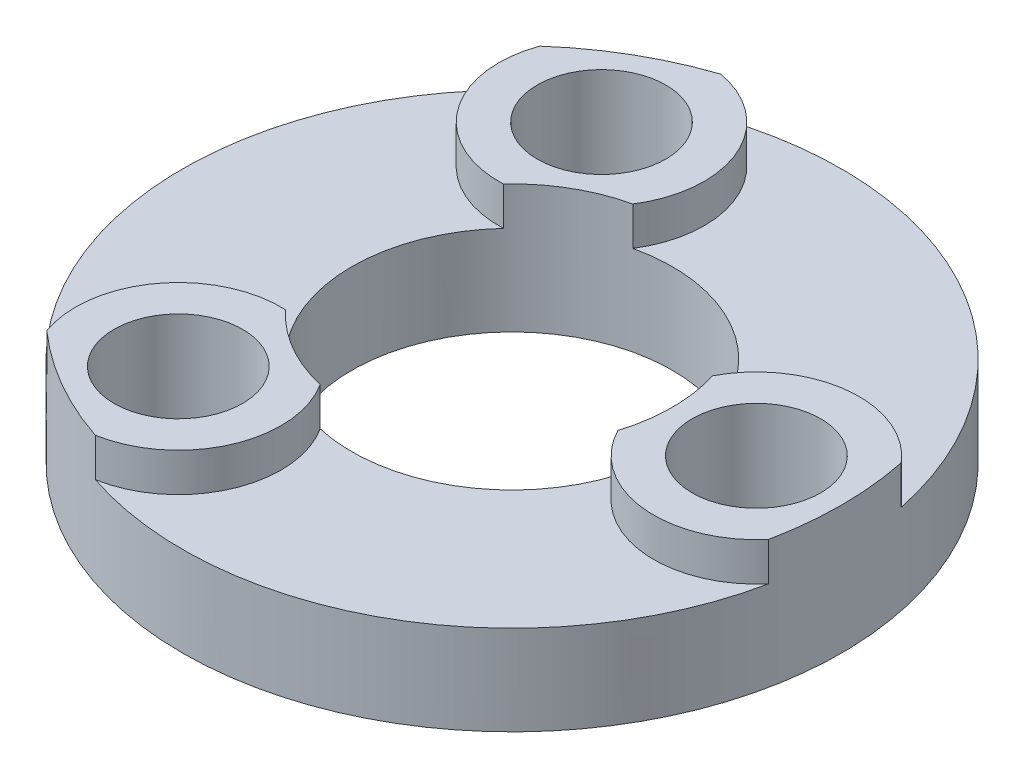
SolidWorks part; units mm, degrees
material "ABS"
ref_plane "Front Plane" through (0, 0, 0) normal (0, 0, 1) x (1, 0, 0)
ref_plane "Top Plane" through (0, 0, 0) normal (0, 1, 0) x (1, 0, 0)
ref_plane "Right Plane" through (0, 0, 0) normal (1, 0, 0) x (0, 0, -1)
sketch "Sketch1" plane through (0, 0, 0) normal (0, 1, 0) x (1, 0, 0)
  circle A2 centre (-9.5263, -16.4999) radius 3.175 construction
  circle A3 centre (-9.5262, 16.4999) radius 3.175 construction
  circle A4 centre (19.0525, 0) radius 3.175 construction
  circle A5 centre (-9.5262, 16.4999) radius 3.175
  circle A6 centre (19.0525, 0) radius 3.175
  circle A7 centre (-9.5263, -16.4999) radius 3.175
  circle A15 centre (0, 0) radius 12.5
  circle A16 centre (0, 0) radius 25.7
  point P1 (30.1365, 0)
  point P12 (-9.5263, -16.4999)
  point P14 (19.0525, 0)
  point P16 (-9.5262, 16.4999)
  point P20 (-4.9245, 20.2425)
  point P29 (-4.9245, -20.2425)
  dimension "D1" = 51.4
  dimension "D3" = 6.35
  dimension "D4" = 25
  dimension "D2" = 19.0525
extrude "Boss-Extrude1" add sketch "Sketch1" along normal blind 10 contours A7 | A5 | A6 | A5 A6 A7 region at (-9.5262, 0, -16.4999) region at (19.0525, 0, 0) region at (-9.5262, 0, 16.4999) region at (-24.9731, 0, 0)
sketch "Sketch3" plane through (0, 10, 0) normal (0, 1, 0) x (1, 0, 0)
  circle A1 centre (19.0525, 0) radius 5.0125
  dimension "D1" = 10.025
extrude "Cut-Extrude1" cut sketch "Sketch3" against normal blind 7.5
sketch "Sketch5" plane through (0, 0, 0) normal (0, 0, 1) x (1, 0, 0)
  line L0 (0, 0) -> (0, 1.348) construction
pattern_circular "CirPattern1" count 3 every 120 about axis through (0, 0, 0) along (0, 1, 0) of "Cut-Extrude1"
sketch "Sketch6" plane through (0, 10, 0) normal (0, 1, 0) x (1, 0, 0)
  circle A6 centre (-9.5262, 16.4999) radius 8.0125
  arc A7 (-17.0638, 19.2176) -> (-9.1694, 8.4954) centre (-9.5262, 16.4999) ccw
  circle A9 centre (19.0525, 0) radius 8.0125
  arc A10 (11.9419, -3.6932) -> (25.1748, -5.1688) centre (19.0525, 0) ccw
  circle A11 centre (0, 0) radius 12.5 construction
  circle A12 centre (-9.5262, -16.4999) radius 8.0125
  arc A13 (-9.1694, -8.4954) -> (-17.0638, -19.2176) centre (-9.5262, -16.4999) ccw
  circle A14 centre (0, 0) radius 25.7 construction
  arc A15 (-2.7725, -12.1886) -> (11.9419, -3.6932) centre (0, 0) ccw
  arc A16 (-8.1111, -24.3865) -> (25.1748, -5.1688) centre (0, 0) ccw
  arc A17 (-2.7725, 12.1886) -> (-8.1111, 24.3865) centre (-9.5262, 16.4999) ccw
  arc A18 (25.1748, 5.1688) -> (11.9419, 3.6932) centre (19.0525, 0) ccw
  arc A19 (-8.1111, -24.3865) -> (-2.7725, -12.1886) centre (-9.5262, -16.4999) ccw
  arc A20 (25.1748, 5.1688) -> (-8.1111, 24.3865) centre (0, 0) ccw
  arc A21 (11.9419, 3.6932) -> (-2.7725, 12.1886) centre (0, 0) ccw
  arc A22 (-9.1694, 8.4954) -> (-9.1694, -8.4954) centre (0, 0) ccw
  arc A23 (-17.0638, 19.2176) -> (-17.0638, -19.2176) centre (0, 0) ccw
  dimension "D1" = 3
  dimension "D2" = 3
  dimension "D3" = 3
extrude "Cut-Extrude2" cut sketch "Sketch6" against normal blind 3
